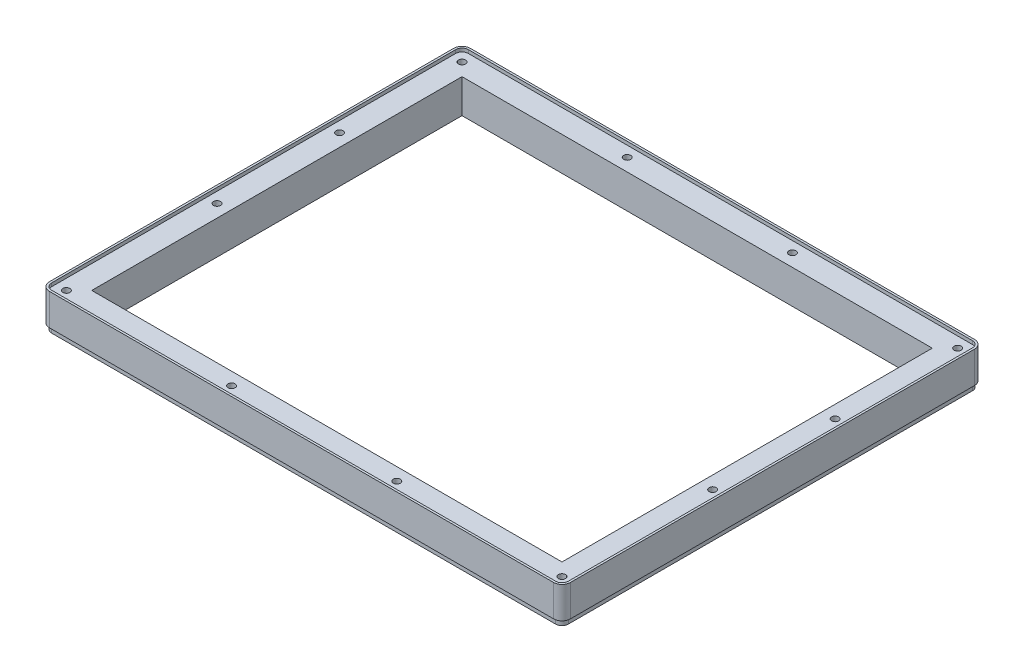
SolidWorks part; units mm, degrees
ref_plane "Front Plane" through (0, 0, 0) normal (0, 0, 1) x (1, 0, 0)
ref_plane "Top Plane" through (0, 0, 0) normal (0, 1, 0) x (1, 0, 0)
ref_plane "Right Plane" through (0, 0, 0) normal (1, 0, 0) x (0, 0, -1)
sketch "Sketch1" plane through (0, 0, 0) normal (0, 1, 0) x (1, 0, 0)
  line L1 (0, 0) -> (164.87, 0)
  line L2 (0, 0) -> (0, -104.3)
  line L3 (0, -104.3) -> (164.87, -104.3)
  line L4 (164.87, 0) -> (164.87, -104.3)
  line L5 (7.23, -7.46) -> (162.2, -7.46)
  line L6 (7.23, -7.46) -> (7.23, -101.93)
  line L7 (7.23, -101.93) -> (162.2, -101.93)
  line L8 (162.2, -7.46) -> (162.2, -101.93)
  line L9 (-4.77, 7.54) -> (174.2, 7.54)
  line L10 (-7.77, 4.54) -> (-7.77, -138.93)
  line L11 (-4.77, -141.93) -> (174.2, -141.93)
  line L12 (177.2, 4.54) -> (177.2, -138.93)
  arc A0 (174.2, -141.93) -> (177.2, -138.93) centre (174.2, -138.93) ccw
  arc A1 (-7.77, -138.93) -> (-4.77, -141.93) centre (-4.77, -138.93) ccw
  arc A2 (-4.77, 7.54) -> (-7.77, 4.54) centre (-4.77, 4.54) ccw
  arc A3 (174.2, 7.54) -> (177.2, 4.54) centre (174.2, 4.54) cw
  dimension "D11" = 3
  dimension "D1" = 104.3
  dimension "D2" = 164.87
  dimension "D3" = 2.67
  dimension "D4" = 2.37
  dimension "D5" = 7.46
  dimension "D6" = 7.23
  dimension "D7" = 15
  dimension "D8" = 15
  dimension "D9" = 15
  dimension "D10" = 40
extrude "Boss-Extrude1" add sketch "Sketch1" against normal blind 12 contours A3 L9 A2 L10 A1 L11 A0 L12 L1 L4 L3 L2 | L4 L1 L2 L3 L5 L8 L7 L6 | L8 L5 L6 L7 region at (82.435, 0, 1.9509) region at (84.715, 0, 54.695) region at (84.715, 0, -5.1619)
sketch "Sketch12" plane through (0, -12, 0) normal (0, -1, 0) x (1, 0, 0)
  line L0 (-4.77, -7.54) -> (174.2, -7.54)
  line L1 (177.2, -4.54) -> (177.2, 138.93)
  line L2 (-4.77, 141.93) -> (174.2, 141.93)
  line L3 (-7.77, -4.54) -> (-7.77, 138.93)
  line L4 (176.45, -4.54) -> (176.45, 138.93)
  line L5 (-4.77, 141.18) -> (174.2, 141.18)
  line L6 (-7.02, -4.54) -> (-7.02, 138.93)
  line L7 (-4.77, -6.79) -> (174.2, -6.79)
  line L8 (176.2, -4.54) -> (176.2, 138.93)
  line L9 (-4.77, -6.54) -> (174.2, -6.54)
  line L10 (176.2, -4.54) -> (176.2, 138.93)
  line L11 (-4.77, -6.54) -> (174.2, -6.54)
  line L18 (-6.77, -4.54) -> (-6.77, 138.93)
  line L19 (-4.77, 140.93) -> (174.2, 140.93)
  line L20 (-6.77, -4.54) -> (-6.77, 138.93)
  line L21 (-4.77, 140.93) -> (174.2, 140.93)
  arc A0 (174.2, -7.54) -> (177.2, -4.54) centre (174.2, -4.54) ccw
  arc A1 (177.2, 138.93) -> (174.2, 141.93) centre (174.2, 138.93) ccw
  arc A2 (-4.77, 141.93) -> (-7.77, 138.93) centre (-4.77, 138.93) ccw
  arc A3 (-7.77, -4.54) -> (-4.77, -7.54) centre (-4.77, -4.54) ccw
  arc A4 (176.45, 138.93) -> (174.2, 141.18) centre (174.2, 138.93) ccw
  arc A5 (-4.77, 141.18) -> (-7.02, 138.93) centre (-4.77, 138.93) ccw
  arc A6 (176.2, 138.93) -> (174.2, 140.93) centre (174.2, 138.93) ccw
  arc A7 (174.2, -6.54) -> (176.2, -4.54) centre (174.2, -4.54) ccw
  arc A8 (176.2, 138.93) -> (174.2, 140.93) centre (174.2, 138.93) ccw
  arc A9 (174.2, -6.54) -> (176.2, -4.54) centre (174.2, -4.54) ccw
  arc A10 (-7.02, -4.54) -> (-4.77, -6.79) centre (-4.77, -4.54) ccw
  arc A11 (174.2, -6.79) -> (176.45, -4.54) centre (174.2, -4.54) ccw
  arc A14 (-6.77, -4.54) -> (-4.77, -6.54) centre (-4.77, -4.54) ccw
  arc A15 (-4.77, 140.93) -> (-6.77, 138.93) centre (-4.77, 138.93) ccw
  arc A16 (-6.77, -4.54) -> (-4.77, -6.54) centre (-4.77, -4.54) ccw
  arc A17 (-4.77, 140.93) -> (-6.77, 138.93) centre (-4.77, 138.93) ccw
  arc M25 (174.2, -7.54) -> (177.2, -4.54) centre (174.2, -4.54) ccw
  line M26 (177.2, -4.54) -> (177.2, 138.93)
  arc M27 (177.2, 138.93) -> (174.2, 141.93) centre (174.2, 138.93) ccw
  line M28 (174.2, 141.93) -> (-4.77, 141.93)
  arc M29 (-4.77, 141.93) -> (-7.77, 138.93) centre (-4.77, 138.93) ccw
  line M30 (-7.77, 138.93) -> (-7.77, -4.54)
  arc M31 (-7.77, -4.54) -> (-4.77, -7.54) centre (-4.77, -4.54) ccw
  line M32 (-4.77, -7.54) -> (174.2, -7.54)
  dimension "D1" = 1
  dimension "D2" = 1
  dimension "D3" = 1
  dimension "D4" = 0.25
sketch "Sketch8" plane through (0, -12, 0) normal (0, -1, 0) x (1, 0, 0)
  line L0 (177.2, -4.54) -> (177.2, 138.93) construction
  line L1 (86.11, 110.85) -> (164.87, 110.85)
  line L2 (86.11, 110.85) -> (86.11, 129.3)
  line L3 (86.11, 129.3) -> (164.87, 129.3)
  line L4 (164.87, 110.85) -> (164.87, 129.3)
  line L5 (-4.77, 141.93) -> (174.2, 141.93) construction
  dimension "D1" = 78.76
  dimension "D2" = 18.45
  dimension "D3" = 12.33
  dimension "D4" = 12.63
sketch "Sketch2" plane through (0, -12, 0) normal (0, -1, 0) x (1, 0, 0)
  line L0 (-7.77, -4.54) -> (-7.77, 138.93) construction
  line L1 (-4.77, -7.54) -> (174.2, -7.54) construction
  line L2 (177.2, -4.54) -> (177.2, 138.93) construction
  line L3 (-4.77, 141.93) -> (174.2, 141.93) construction
  circle A0 centre (-3.27, -3.04) radius 1.25
  circle A1 centre (172.7, -3.04) radius 1.25
  circle A2 centre (172.7, 137.43) radius 1.25
  circle A3 centre (-3.27, 137.43) radius 1.25
  circle A4 centre (-3.27, 40.45) radius 1.25
  circle A5 centre (-3.27, 83.94) radius 1.25
  circle A6 centre (172.7, 40.45) radius 1.25
  circle A7 centre (172.7, 83.94) radius 1.25
  circle A8 centre (114.05, -3.04) radius 1.25
  circle A9 centre (55.38, -3.04) radius 1.25
  circle A10 centre (114.05, 137.43) radius 1.25
  circle A11 centre (55.38, 137.43) radius 1.25
  dimension "D1" = 2.5
  dimension "D4" = 2.5
  dimension "D6" = 2.5
  dimension "D8" = 2.5
  dimension "D9" = 2.5
  dimension "D10" = 2.5
  dimension "D13" = 2.5
  dimension "D14" = 2.5
  dimension "D17" = 2.5
  dimension "D18" = 2.5
  dimension "D19" = 2.5
  dimension "D20" = 2.5
  dimension "D2" = 4.5
  dimension "D3" = 4.5
  dimension "D5" = 4.5
  dimension "D7" = 4.5
  dimension "D11" = 43.49
  dimension "D12" = 43.49
  dimension "D21" = 58.65
  dimension "D22" = 58.65
extrude "Cut-Extrude3" cut sketch "Sketch2" against normal up to next contours A1 | A8 | A0 | A5 | A3 | A11 | A10 | A2 | A7 | A6 | A9 | A4 region at (-3.27, -12, -3.04) region at (172.7, -12, -3.04) region at (172.7, -12, 137.43) region at (-3.27, -12, 137.43) region at (-3.27, -12, 83.94) region at (172.7, -12, 40.45) region at (172.7, -12, 83.94) region at (114.05, -12, -3.04) region at (114.05, -12, 137.43) region at (55.38, -12, 137.43)
extrude "Boss-Extrude2" add sketch "Sketch12" against normal blind 1.2 from surface contours A11 L7 A10 L6 A5 L5 A4 L4 M32 M25 M26 M27 M28 M29 M30 M31 region at (-6.7232, -12, -6.4932) starting at face at (172.7, 0, 85.19)
sketch "Sketch13" plane through (0, -12, 0) normal (0, -1, 0) x (1, 0, 0)
  line L0 (-4.77, -7.54) -> (174.2, -7.54) construction
  line L1 (168.2, 1.46) -> (1.23, 1.46)
  line L2 (168.2, 1.46) -> (168.2, 132.93)
  line L3 (168.2, 132.93) -> (1.23, 132.93)
  line L4 (1.23, 1.46) -> (1.23, 132.93)
  line L5 (177.2, -4.54) -> (177.2, 138.93) construction
  line L6 (-4.77, 141.93) -> (174.2, 141.93) construction
  line L7 (-7.77, -4.54) -> (-7.77, 138.93) construction
  dimension "D1" = 9
  dimension "D2" = 9
  dimension "D3" = 9
  dimension "D4" = 9
extrude "Cut-Extrude4" cut sketch "Sketch13" against normal up to next
extrude "Cut-Extrude5" cut sketch "Sketch12<4>" against normal blind 2 from surface contours A11 L7 A10 L6 A5 L5 A4 L4 M32 M25 M26 M27 M28 M29 M30 M31 region at (-6.7232, -12, -6.4932) starting at face at (84.715, -12, 67.195)
sketch "Sketch12<4>" plane through (0, -12, 0) normal (0, -1, 0) x (1, 0, 0) same geometry as "Sketch12"
